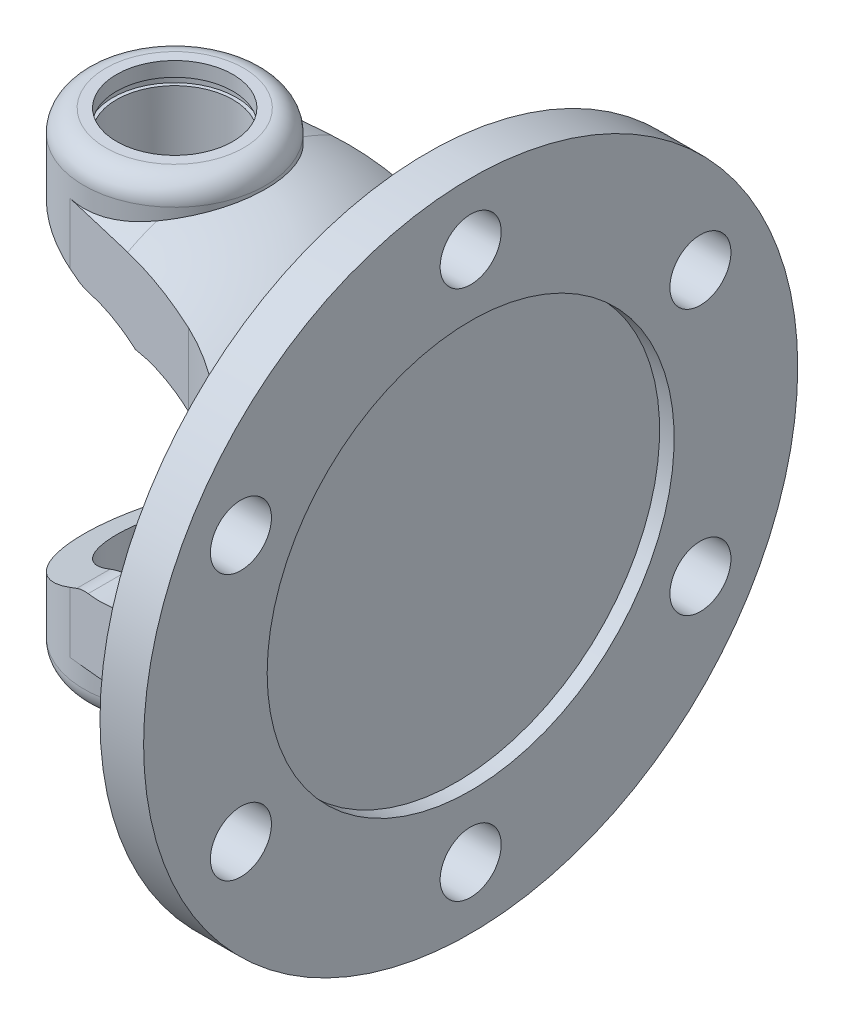
SolidWorks part; units mm, degrees
ref_plane "Front Plane" through (0, 0, 0) normal (0, 0, 1) x (1, 0, 0)
ref_plane "Top Plane" through (0, 0, 0) normal (0, 1, 0) x (1, 0, 0)
ref_plane "Right Plane" through (0, 0, 0) normal (1, 0, 0) x (0, 0, -1)
sketch "Sketch1" plane through (0, 0, 0) normal (0, 0, 1) x (1, 0, 0)
  line L0 (-12.5, 0) -> (38.7164, 0)
  line L1 (38.7164, 0) -> (38.7164, 28)
  line L2 (38.7164, 28) -> (40.7164, 28)
  line L3 (7.5, 30) -> (-12.5, 30)
  line L4 (-12.5, 30) -> (-12.5, 0)
  line L5 (40.7164, 28) -> (40.7164, 45)
  line L6 (40.7164, 45) -> (34.7164, 45)
  line L7 (30.7164, 19) -> (34.7164, 19)
  line L8 (34.7164, 19) -> (34.7164, 45)
  arc A0 (30.7164, 19) -> (7.5, 30) centre (7.5, 0) ccw
  dimension "D3" = 30
  dimension "D4" = 45
  dimension "D2" = 30
  dimension "D5" = 12.5
  dimension "D6" = 20
  dimension "D7" = 6
  dimension "D8" = 2
  dimension "D9" = 28
  dimension "D10" = 4
  dimension "D11" = 19
revolve "Revolve1" add sketch "Sketch1" angle 360 about L0
sketch "Sketch2" plane through (0, 0, 0) normal (0, 1, 0) x (1, 0, 0)
  line L0 (28.5, -21.4243) -> (28.5, -41.4243)
  line L1 (28.5, -21.4243) -> (25.0936, -24.7633) construction
  line L2 (28.5, -21.4243) -> (29.6509, -22.5985) construction
  line L3 (-12.5, 0) -> (41.0657, 0) construction
  line L4 (-12.5, 30) -> (-12.5, -30) construction
  line L5 (-2.1199, -12.3189) -> (17.609, -15.714)
  line L6 (-2.1199, 12.3189) -> (17.609, 15.714)
  line L7 (28.5, -41.4243) -> (-41.5, -41.4243)
  line L8 (-41.5, -41.4243) -> (-41.5, 41.4243)
  line L9 (-41.5, 41.4243) -> (28.5, 41.4243)
  line L10 (28.5, 41.4243) -> (28.5, 21.4243)
  arc A0 (-2.1199, 12.3189) -> (-2.1199, -12.3189) centre (0, 0) ccw
  arc A2 (17.609, -15.714) -> (28.5, -21.4243) centre (14.2171, -35.4243) cw
  arc A3 (7.5, -30) -> (30.7164, -19) centre (7.5, 0) ccw construction
  arc A4 (7.5, -30) -> (30.7164, -19) centre (7.5, 0) ccw construction
  arc A5 (7.5, -30) -> (30.7164, -19) centre (7.5, 0) ccw construction
  arc A6 (17.609, 15.714) -> (28.5, 21.4243) centre (14.2171, 35.4243) ccw
  dimension "D1" = 25
  dimension "D2" = 20
  dimension "D3" = 20
  dimension "D4" = 70
  dimension "D5" = 41
extrude "Cut-Extrude1" cut sketch "Sketch2" against normal through all both and the other way through all
sketch "Sketch3" plane through (0, 0, 0) normal (0, 0, 1) x (1, 0, 0)
  line L0 (-12.5, 24) -> (0, 18)
  line L1 (-12.5, 30) -> (-12.5, -30) construction
  line L4 (0, 18) -> (0, -18)
  line L5 (24, 0) -> (0, 0) construction
  line L7 (-12.5, -24) -> (0, -18)
  line L9 (-12.5, 24) -> (-12.5, -24)
  dimension "D1" = 12.5
  dimension "D3" = 6
  dimension "D4" = 12
extrude "Cut-Extrude2" cut sketch "Sketch3" against normal through all both and the other way through all
sketch "Sketch7" plane through (0, 0, 0) normal (1, 0, 0) x (0, 0, -1)
  line L0 (0, 0) -> (0, 43.6765) construction
  line L1 (-20, 18) -> (-8, 18)
  line L2 (12.6837, 18) -> (-12.6837, 18) construction
  line L5 (20, 18) -> (8, 18)
  line L6 (-20, 18) -> (-20, 0)
  line L8 (-20, 0) -> (20, 0)
  line L9 (20, 0) -> (20, 18)
  arc A0 (8, 18) -> (-8, 18) centre (0, 0) ccw
  dimension "D1" = 16
  dimension "D3" = 40
revolve "Cut-Revolve2" cut sketch "Sketch7" angle 360 about L8
fillet "Fillet1" radius 5 4 edges at (0, -18, -10.3419) (0, -18, 10.3419) (0, 18, -10.3419) (0, 18, 10.3419)
sketch "Sketch4" plane through (0, 0, 0) normal (0, 0, 1) x (1, 0, 0)
  line L0 (-9.5, 33) -> (0, 33)
  line L1 (0, 33) -> (0, 24)
  line L2 (0, 24) -> (-12.5, 24)
  line L3 (-12.5, 30) -> (-12.5, 24) construction
  line L4 (-12.5, 24) -> (-12.5, 30)
  line L5 (7.5, 30) -> (-12.5, 30) construction
  arc A0 (-12.5, 30) -> (-9.5, 33) centre (-9.5, 30) cw
  dimension "D1" = 3
revolve "Revolve2" add sketch "Sketch4" angle 360 about L1
mirror "Mirror1" about plane through (0, 0, 0) normal (0, 1, 0) of "Revolve2"
sketch "Sketch5" plane through (0, 33, 0) normal (0, 1, 0) x (1, 0, 0)
  circle A0 centre (0, 0) radius 8
  dimension "D1" = 16
extrude "Cut-Extrude3" cut sketch "Sketch5" against normal through all
sketch "Sketch6" plane through (0, 0, 0) normal (0, 0, 1) x (1, 0, 0)
  line L0 (8, 31) -> (8.5, 31)
  line L1 (8.5, 31) -> (8.5, 30)
  line L2 (8.5, 30) -> (8, 30)
  line L3 (8, 30) -> (8, 31)
  line L4 (0, 0) -> (0, 47.1154) construction
  line L5 (9.5, 33) -> (-9.5, 33) construction
  line L7 (0, 0) -> (51.1336, 0) construction
  line L8 (8, -30) -> (8, -31)
  line L9 (8.5, -30) -> (8, -30)
  line L10 (8.5, -31) -> (8.5, -30)
  line L11 (8, -31) -> (8.5, -31)
  dimension "D1" = 8
  dimension "D2" = 2
  dimension "D3" = 1
  dimension "D4" = 0.5
revolve "Cut-Revolve1" cut sketch "Sketch6" angle 360 about L4
sketch "Sketch8" plane through (0, 0, 0) normal (0, 1, 0) x (1, 0, 0)
  line L0 (19.374, 3.5567) -> (6.3836, 11.0567)
  line L1 (-11.0329, -19.1096) -> (22.7452, 39.3958) construction
  line L4 (6.3836, 11.0567) -> (14.5636, 25.2249)
  line L5 (14.5636, 25.2249) -> (25.5, 18.9107)
  line L6 (0, 0) -> (0, 51.0803) construction
  line L7 (18, 15.7853) -> (18, 8)
  line L8 (18, 15.7853) -> (18, 8) construction
  arc A0 (19.374, 3.5567) -> (25.5, 18.9107) centre (5.5215, 17.9827) ccw
  arc A1 (18, 15.7853) -> (28.5, 21.4243) centre (14.2171, 35.4243) ccw
  arc A2 (18, 15.7853) -> (28.5, 21.4243) centre (14.2171, 35.4243) ccw construction
  arc A3 (18, -8) -> (18, 8) centre (0, 0) ccw
  arc A4 (18, -8) -> (18, 8) centre (0, 0) ccw construction
  point P15 (25.5, 18.9107)
  dimension "D1" = 15
  dimension "D4" = 3
  dimension "D2" = 30
  dimension "D3" = 20
revolve "Cut-Revolve3" cut sketch "Sketch8" angle 360 about L1
mirror "Mirror2" about plane through (0, 0, 0) normal (0, 0, 1) of "Cut-Revolve3"
hole_wizard "M8 Clearance Hole1" positions "Sketch11" profile "Sketch10" hole size "M8" standard "DIN" end condition up to next
sketch "Sketch11" plane through (40.7164, 0, 0) normal (1, 0, 0) x (0, 0, -1)
  line L0 (0, 28) -> (0, 45) construction
  circle A0 centre (0, 0) radius 28 construction
  circle A1 centre (0, 0) radius 28 construction
  circle A2 centre (0, 0) radius 45 construction
  point P0 (0, 36.5)
sketch "Sketch10" plane through (40.7164, 36.5, 0) normal (0, 1, 0) x (0, 0, -1)
  line L0 (0, 0) -> (0, 6.001)
  line L1 (0, 6.001) -> (4.2, 6.001)
  line L2 (4.2, 6.001) -> (4.2, 0)
  line L5 (4.2, 0) -> (0, 0)
  line L11 (0, -6.35) -> (0, 107.95) construction
  dimension "Thru Hole Dia." = 8.4
  dimension "Thru Hole Depth" = 6.001
pattern_circular "CirPattern1" count 6 over 360 about axis through (-12.5, 0, 0) along (-1, 0, 0) of "M8 Clearance Hole1"
chamfer "Chamfer1" distance 1.5 angle 45 1 edges at (34.7164, 0, 19)
